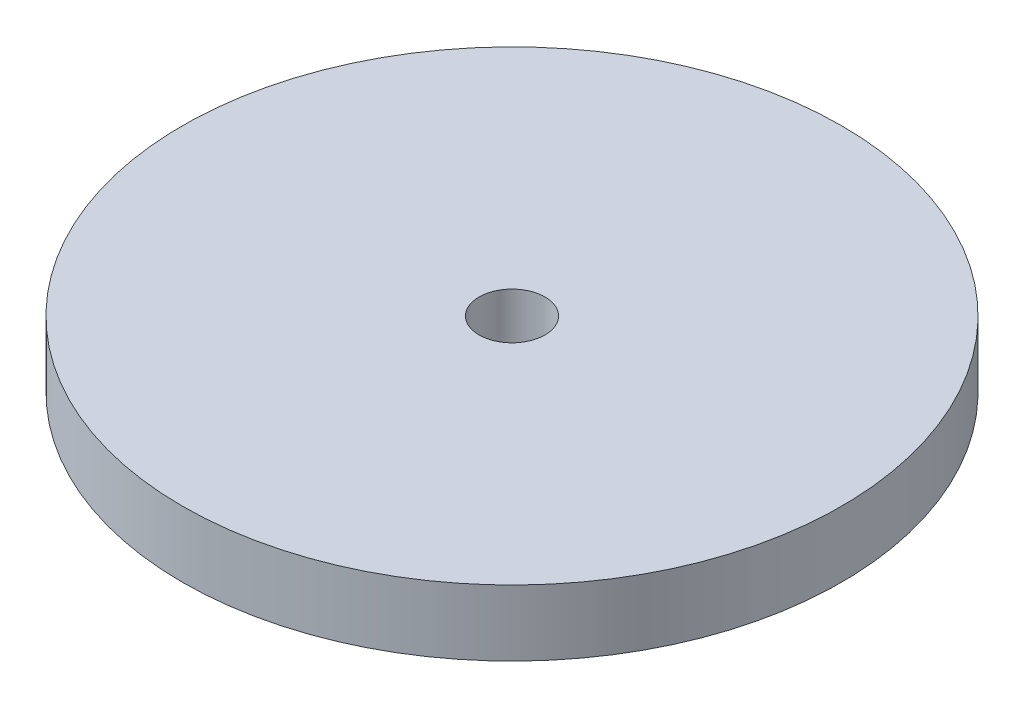
SolidWorks part; units mm, degrees
ref_plane "Front Plane" through (0, 0, 0) normal (0, 0, 1) x (1, 0, 0)
ref_plane "Top Plane" through (0, 0, 0) normal (0, 1, 0) x (1, 0, 0)
ref_plane "Right Plane" through (0, 0, 0) normal (1, 0, 0) x (0, 0, -1)
sketch "Sketch1" plane through (0, 0, 0) normal (0, 1, 0) x (1, 0, 0)
  line L0 (0, -38.1) -> (0, 47.0942) construction
  line L4 (44.7892, 14.5529) -> (0, 47.0942) construction
  line L5 (0, 47.0942) -> (-44.7892, 14.5529) construction
  line L6 (-44.7892, 14.5529) -> (36.2353, -11.7735) construction
  line L7 (44.7892, 14.5529) -> (-36.2353, -11.7735) construction
  line L8 (-27.6813, -38.1) -> (22.3946, 30.8235) construction
  line L9 (-44.7892, 14.5529) -> (-27.6813, -38.1) [skipped]
  line L10 (-27.6813, -38.1) -> (27.6813, -38.1) [skipped]
  line L11 (27.6813, -38.1) -> (44.7892, 14.5529) [skipped]
  circle A0 centre (0, 0) radius 31.75
  dimension "D1" = 63.5
extrude "Boss-Extrude1" add sketch "Sketch1" along normal blind 6.35
sketch "Sketch2" plane through (0, 6.35, 0) normal (0, 1, 0) x (1, 0, 0)
  circle A0 centre (0, 0) radius 3.175
  dimension "D1" = 6.35
extrude "Cut-Extrude1" cut sketch "Sketch2" against normal through all
